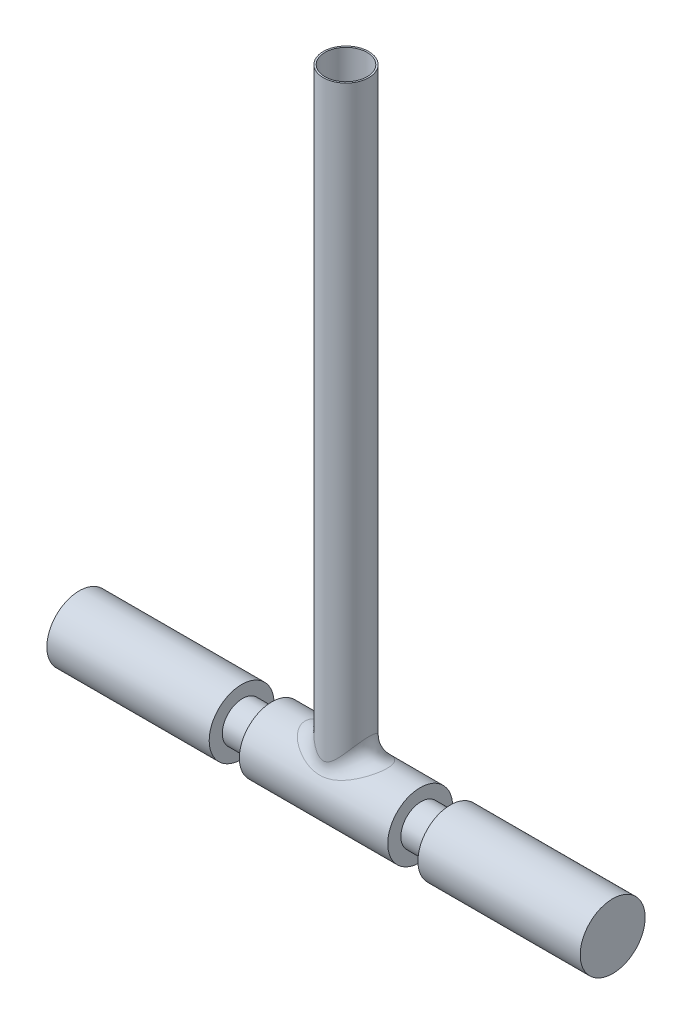
SolidWorks part; units mm, degrees
ref_plane "Front Plane" through (0, 0, 0) normal (0, 0, 1) x (1, 0, 0)
ref_plane "Top Plane" through (0, 0, 0) normal (0, 1, 0) x (1, 0, 0)
ref_plane "Right Plane" through (0, 0, 0) normal (1, 0, 0) x (0, 0, -1)
sketch "Sketch1" plane through (0, 0, 0) normal (0, 1, 0) x (1, 0, 0)
  circle A0 centre (0, 0) radius 12.446
extrude "Boss-Extrude1" add sketch "Sketch1" along normal blind 340.36
sketch "Sketch2" plane through (0, 340.36, 0) normal (0, 1, 0) x (1, 0, 0)
  circle A0 centre (0, 0) radius 11.5531
extrude "Cut-Extrude1" cut sketch "Sketch2" against normal blind 304.8 contours A0
sketch "Sketch4" plane through (0, 10.4843, 0) normal (1, 0, 0) x (0, 0, -1)
  circle A0 centre (0.4491, -10.6731) radius 11.049
extrude "Boss-Extrude4" add sketch "Sketch4" along normal mid plane 292.1
sketch "Sketch5" plane through (0, 0, 0) normal (1, 0, 0) x (0, 0, -1)
  circle A0 centre (0, 0) radius 17.78
extrude "Boss-Extrude5" add sketch "Sketch5" along normal mid plane 81.28
sketch "Sketch7" plane through (146.05, 0, 0) normal (1, 0, 0) x (0, 0, -1)
  circle A0 centre (0, 0) radius 17.78
extrude "Boss-Extrude6" add sketch "Sketch7" against normal blind 88.9
sketch "Sketch8" plane through (-146.05, 0, 0) normal (-1, 0, 0) x (0, 0, 1)
  circle A0 centre (0, 0) radius 17.78
extrude "Boss-Extrude7" add sketch "Sketch8" against normal blind 88.9
fillet "Fillet2" radius 10 1 edges at (-1.5754, 12.7948, 12.3459)
